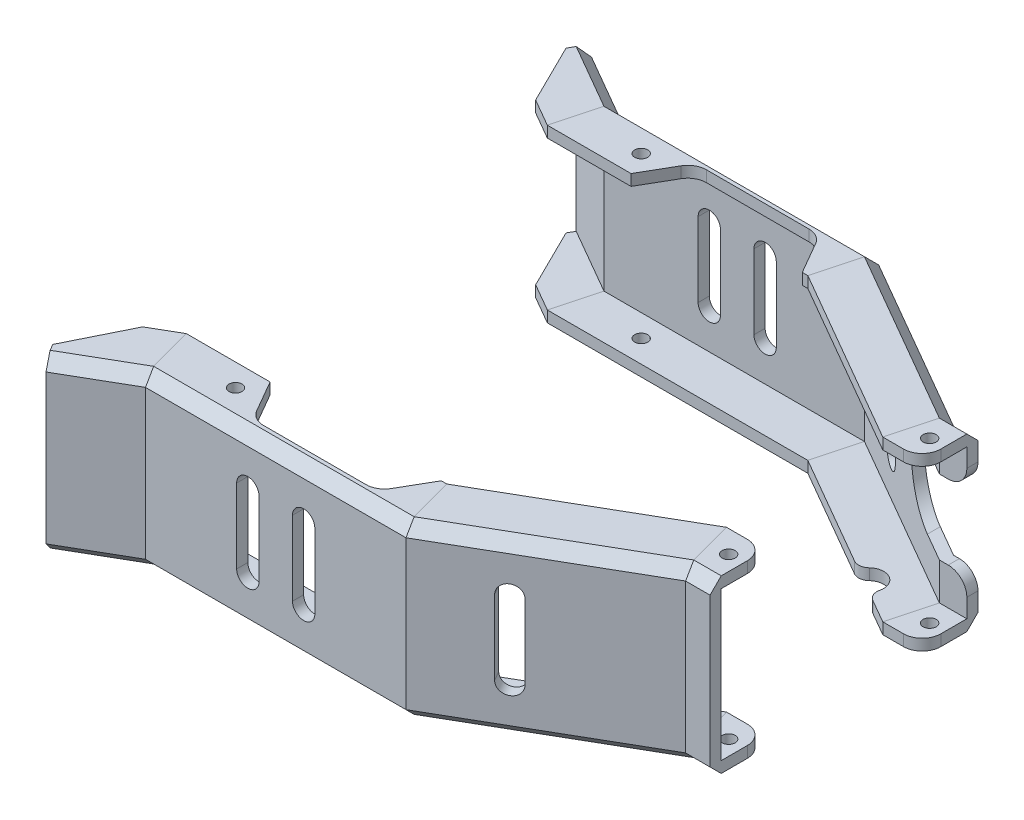
SolidWorks part; units mm, degrees
material "ABS PC"
ref_plane "Front Plane" through (0, 0, 0) normal (0, 0, 1) x (1, 0, 0)
ref_plane "Top Plane" through (0, 0, 0) normal (0, 1, 0) x (1, 0, 0)
ref_plane "Right Plane" through (0, 0, 0) normal (1, 0, 0) x (0, 0, -1)
sketch "Sketch6" plane through (0, 0, 0) normal (0, 1, 0) x (1, 0, 0)
  line L0 (0, 0) -> (-70, 0)
  line L1 (-70, 0) -> (-87.3205, -10)
  line L2 (0, 0) -> (47.6314, 27.5)
  line L3 (47.6314, 27.5) -> (54.6314, 27.5)
  dimension "D1" = 70
  dimension "D2" = 20
  dimension "D3" = 150
  dimension "D4" = 55
  dimension "D5" = 7
ref_plane "Plane5" through (0, 0, 0) normal (1, 0, 0) x (0, 0, -1)
sketch "Sketch7" plane through (0, 0, 0) normal (1, 0, 0) x (0, 0, -1)
  line L0 (1.3953, 0) -> (11.0315, 0) construction
  line L2 (-1.6047, -23) -> (-1.6047, 23)
  line L4 (1.3953, -20) -> (1.3953, 20)
  line L5 (-1.6047, -23) -> (1.3953, 20) construction
  line L6 (-1.6047, 23) -> (1.3953, -20) construction
  line L7 (13.3953, 20) -> (13.3953, 23)
  line L8 (1.3953, -20) -> (13.3953, -20)
  line L10 (-1.6047, -23) -> (13.3953, -23)
  line L11 (13.3953, -20) -> (13.3953, -23)
  line L12 (-1.6047, 23) -> (13.3953, 23)
  line L14 (1.3953, 20) -> (13.3953, 20)
  point P0 (0, 0)
  dimension "D1" = 3
  dimension "D3" = 3
  dimension "D2" = 40
  dimension "D5" = 15
sweep "Sweep8" add profiles "Sketch7" path "Sketch6"
ref_plane "Plane6" through (0, 0, -61.8953) normal (0, 0, -1) x (-1, 0, 0)
sketch "Sketch8" plane through (0, 23, 0) normal (0, 1, 0) x (1, 0, 0)
  line L1 (-73.5893, 13.3953) -> (-94.0182, 1.6007) construction
  line L3 (-89.0182, -7.0595) -> (-94.0182, 1.6007)
  line L4 (-94.0182, 1.6007) -> (-81.0278, 9.1007)
  line L5 (-94.0182, 1.6007) -> (-86.5182, -11.3897) construction
  line L6 (-81.0278, 9.1007) -> (-89.0182, -7.0595)
  dimension "D1" = 15
  dimension "D2" = 10
extrude "Cut-Extrude1" cut sketch "Sketch8" against normal through all
sketch "Sketch10" plane through (0, 23, 0) normal (0, 1, 0) x (1, 0, 0)
  line L0 (-3.5893, 13.3953) -> (-73.5893, 13.3953) construction
  line L1 (-51.0893, 13.3953) -> (-5.0893, 13.3953)
  line L5 (-5.0893, 13.3953) -> (-11.4401, 2.3953)
  line L6 (-11.4401, 2.3953) -> (-44.7384, 2.3953)
  line L7 (-28.0893, 2.3953) -> (-28.0893, 13.3953) construction
  line L8 (-51.0893, 13.3953) -> (-44.7384, 2.3953)
  point P1 (-14.8566, 0)
  point P6 (-28.0893, 13.3953)
  point P9 (-6.1228, 13.3953)
  point P14 (0, 0)
  dimension "D1" = 11
  dimension "D2" = 46
  dimension "D3" = 24.5
  dimension "D4" = 60
extrude "Cut-Extrude3" cut sketch "Sketch10" against normal blind 5
sketch "Sketch11" plane through (0, 0, 1.6047) normal (0, 0, 1) x (1, 0, 0)
  line L0 (-34.57, 23) -> (-34.57, -23) construction
  line L3 (-42.07, -10) -> (-42.07, 10) construction
  line L4 (-45.07, -10) -> (-45.07, 10)
  line L5 (-39.07, -10) -> (-39.07, 10)
  line L6 (-27.07, -10) -> (-27.07, 10) construction
  line L7 (-24.07, -10) -> (-24.07, 10)
  line L8 (-30.07, -10) -> (-30.07, 10)
  line L9 (-34.57, 0) -> (-42.07, 0) construction
  line L11 (0.43, -23) -> (-69.57, -23) construction
  arc A0 (-45.07, -10) -> (-39.07, -10) centre (-42.07, -10) ccw
  arc A1 (-39.07, 10) -> (-45.07, 10) centre (-42.07, 10) ccw
  arc A2 (-24.07, -10) -> (-30.07, -10) centre (-27.07, -10) cw
  arc A3 (-30.07, 10) -> (-24.07, 10) centre (-27.07, 10) cw
  point P2 (-34.57, 21.737)
  point P8 (-42.07, 0)
  point P15 (-27.07, 0)
  dimension "D1" = 15
  dimension "D2" = 6
  dimension "D3" = 20
  dimension "D4" = 23
extrude "Cut-Extrude4" cut sketch "Sketch11" against normal blind 10
chamfer "Chamfer1" distance 3 angle 45 8 edges at (-78.0441, -23, 6.4972) (-34.57, -23, 1.6047) (24.2457, -23, -12.1453) (-78.0441, 23, 6.4972) (-34.57, 23, 1.6047) (24.2457, 23, -12.1453) (51.3464, -23, -25.8953) (51.3464, 23, -25.8953)
sketch "Sketch14" plane through (0.8023, 0, 1.3897) normal (0.5, 0, 0.866) x (0.866, 0, -0.5)
  line L0 (20, -10) -> (20, 10) construction
  line L1 (17, -10) -> (17, 10)
  line L2 (23, -10) -> (23, 10)
  line L5 (0, 0) -> (20, 0) construction
  arc A0 (17, -10) -> (23, -10) centre (20, -10) ccw
  arc A1 (23, 10) -> (17, 10) centre (20, 10) ccw
  point P2 (20, 0)
  dimension "D1" = 20
  dimension "D2" = 6
  dimension "D3" = 20
extrude "Cut-Extrude6" cut sketch "Sketch14" against normal blind 3
hole_wizard "Ø3.5 (3.5) Diameter Hole1" positions "Sketch18" profile "Sketch19" hole size "Ø3.5" standard "ANSI Metric" end condition through all
sketch "Sketch18" plane through (0, -23, 0) normal (0, -1, 0) x (-1, 0, 0)
  line L6 (-50.6314, 34.8953) -> (-50.6314, 28.8953) construction
  line L7 (-54.6314, 28.8953) -> (-47.2575, 28.8953) construction
  line L11 (54.3686, 7.3953) -> (54.3686, 1.3953) construction
  line L12 (0.3739, 1.3953) -> (70.3739, 1.3953) construction
  line L14 (-54.6314, 28.8953) -> (-54.6314, 40.8953) construction
  point P0 (54.3686, 7.3953)
  point P2 (-50.6314, 34.8953)
  dimension "D1" = 6
  dimension "D2" = 105
  dimension "D3" = 4
sketch "Sketch19" plane through (-54.3686, -23, -7.3953) normal (1, 0, 0) x (0, 0, -1)
  line L0 (0, 0) -> (0, 46)
  line L1 (0, 46) -> (1.75, 46)
  line L2 (1.75, 46) -> (1.75, 0)
  line L5 (1.75, 0) -> (0, 0)
  line L11 (0, -6.35) -> (0, 107.95) construction
  dimension "Thru Hole Dia." = 3.5
  dimension "Thru Hole Depth" = 46
sketch "Sketch22" plane through (0, -23, 0) normal (0, -1, 0) x (1, 0, 0)
  line L0 (28.4537, -31.8953) -> (35.3819, -35.8953)
  line L1 (28.4537, -31.8953) -> (28.9537, -31.0293)
  line L2 (35.3819, -35.8953) -> (35.8819, -35.0293)
  line L3 (28.9537, -31.0293) -> (35.8819, -35.0293)
  line L4 (44.0421, -40.8953) -> (-3.5893, -13.3953) construction
  arc A0 (28.9537, -31.0293) -> (35.8819, -35.0293) centre (32.4178, -33.0293) cw
  point P6 (31.9178, -33.8953)
  line M7 (-3.5893, -13.3953) -> (44.0421, -40.8953)
  dimension "D1" = 1
  dimension "D2" = 8
  dimension "D3" = 14
extrude "Cut-Extrude9" cut sketch "Sketch22" against normal blind 10 contours A0 L3 | L3 L1 L2 M7 region at (32.1678, -23, -33.4623) region at (33.2666, -23, -31.5591)
mirror "Mirror2" about plane through (0, 0, -61.8953) normal (0, 0, -1) of bodies 116 103
sketch "Sketch20" plane through (0, 0, -97.8953) normal (0, 0, -1) x (-1, 0, 0)
  line L0 (-54.6314, 0) -> (-47.1314, 0) construction
  line L1 (-54.6314, 20) -> (-54.6314, -20) construction
  line L3 (-39.6314, -10) -> (-54.6314, -10)
  line L4 (-39.6314, -10) -> (-39.6314, 10)
  line L5 (-39.6314, 10) -> (-54.6314, 10)
  line L6 (-54.6314, -10) -> (-54.6314, 10)
  line L7 (-39.6314, -10) -> (-54.6314, 10) construction
  line L8 (-39.6314, 10) -> (-54.6314, -10) construction
  arc A0 (-39.6314, 10) -> (-39.6314, -10) centre (-39.6314, 0) cw
  point P5 (-47.1314, 0)
  line M3 (-48.0614, -20) -> (-48.0614, 20)
  line M5 (-54.6314, 20) -> (-54.6314, -20)
  dimension "D1" = 20
  dimension "D2" = 15
extrude "Cut-Extrude7" cut sketch "Sketch20" against normal blind 5 and the other way through all contours A0 L4 | L5 L3 M3 M5 | L4 L5 L3 M3 region at (43.8464, 0, -97.8953) region at (35.3873, 0, -97.8953) region at (51.3464, 0, -97.8953)
sketch "Sketch21" plane through (0, 0, -25.8953) normal (0, 0, 1) x (1, 0, 0)
  line L0 (54.6314, 0) -> (49.6314, 0) construction
  line L2 (54.6314, 20) -> (54.6314, -20) construction
  line L3 (54.6314, -7.5) -> (44.6314, -7.5)
  line L4 (54.6314, -7.5) -> (54.6314, 7.5)
  line L5 (54.6314, 7.5) -> (44.6314, 7.5)
  line L6 (44.6314, -7.5) -> (44.6314, 7.5)
  line L7 (54.6314, -7.5) -> (44.6314, 7.5) construction
  line L8 (54.6314, 7.5) -> (44.6314, -7.5) construction
  arc A0 (44.6314, 7.5) -> (44.6314, -7.5) centre (44.6314, 0) ccw
  point P5 (49.6314, 0)
  line M14 (48.0614, 20) -> (48.0614, -20)
  line M16 (54.6314, -20) -> (54.6314, 20)
  dimension "D1" = 15
  dimension "D2" = 10
extrude "Cut-Extrude8" [suppressed] cut sketch "Sketch21" against normal blind 10 and the other way blind 10 contours A0 M14 | L6 A0 M14 | L6 L3 L5 M16
fillet "Fillet1" radius 3 2 edges at (28.4537, -21.5, -31.8953) (35.3819, -21.5, -35.8953)
fillet "Fillet2" radius 3 2 edges at (28.4537, -21.5, -91.8953) (35.3819, -21.5, -87.8953)
fillet "Fillet3" radius 5 2 edges at (54.6314, 21.5, -40.8953) (54.6314, -21.5, -40.8953)
fillet "Fillet4" radius 5 2 edges at (54.6314, 21.5, -82.8953) (54.6314, -21.5, -82.8953)
fillet "Fillet5" radius 5 2 edges at (54.6314, 10, -96.3953) (54.6314, -10, -96.3953)
fillet "Fillet6" radius 5 2 edges at (-44.7384, 21.5, -2.3953) (-11.4401, 21.5, -2.3953)
fillet "Fillet7" radius 5 2 edges at (-44.7384, 21.5, -121.3953) (-11.4401, 21.5, -121.3953)
